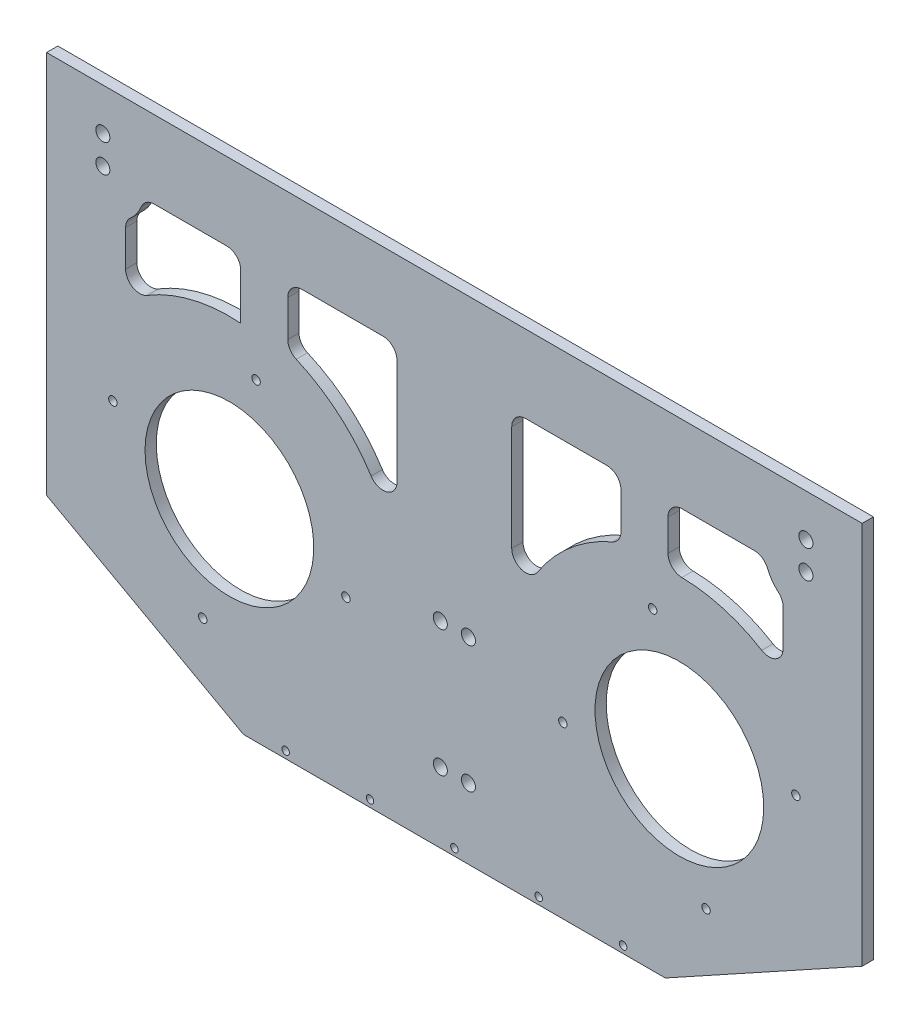
SolidWorks part; units mm, degrees
ref_plane "Front Plane" through (0, 0, 0) normal (0, 0, 1) x (1, 0, 0)
ref_plane "Top Plane" through (0, 0, 0) normal (0, 1, 0) x (1, 0, 0)
ref_plane "Right Plane" through (0, 0, 0) normal (1, 0, 0) x (0, 0, -1)
sketch "Sketch1" plane through (0, 0, 0) normal (0, 0, 1) x (1, 0, 0)
  line L0 (-125, 100) -> (125, 100) construction
  line L1 (-125, 0) -> (125, 0) construction
  line L2 (-145, -16.3871) -> (-75, -55)
  line L3 (-75, -55) -> (75, -55)
  line L4 (75, -55) -> (145, -16.3871)
  line L5 (-125, 105) -> (-125, 95) construction
  line L6 (0, -55) -> (0, 100) construction
  line L7 (-145, 120) -> (145, 120)
  line L8 (145, 120) -> (145, -16.3871)
  line L11 (-145, -16.3871) -> (-145, 120)
  line L12 (125, 105) -> (125, 95) construction
  line L13 (-5, -30) -> (5, -30) construction
  circle A0 centre (-125, 100) radius 12.5 construction
  circle A10 centre (-125, 0) radius 12.5 construction
  circle A11 centre (125, 0) radius 12.5 construction
  circle A12 centre (-125, 0) radius 17.5 construction
  circle A13 centre (-125, 100) radius 17.5 construction
  circle A25 centre (-125, 95) radius 2.5
  circle A26 centre (-125, 105) radius 2.5
  circle A27 centre (125, 95) radius 2.5
  circle A28 centre (125, 105) radius 2.5
  circle A29 centre (5, -30) radius 2.5
  circle A30 centre (-5, -30) radius 2.5
  point P12 (0, 100)
  point P15 (0, -30)
  point P45 (0, 120)
  dimension "D1" = 25
  dimension "D2" = 5
  dimension "D4" = 100
  dimension "D6" = 5
  dimension "D11" = 20
  dimension "D12" = 20
  dimension "D7" = 10
  dimension "D8" = 250
  dimension "D3" = 25
  dimension "D5" = 30
  dimension "D9" = 150
extrude "Boss-Extrude1" add sketch "Sketch1" along normal blind 4
sketch "Sketch2" plane through (0, 0, 4) normal (0, 0, 1) x (1, 0, 0)
  line L0 (121.4264, 24.4924) -> (38.5736, 5.5076) construction
  line L1 (89.4924, -26.4264) -> (70.5076, 56.4264) construction
  line L2 (0, 0) -> (0, 96.4486) construction
  line L3 (145, 120) -> (-145, 120) construction
  line L4 (-145, 120) -> (-145, -16.3871) construction
  line L5 (-80, 15) -> (80, 15) construction
  line L6 (-5, 15) -> (5, 15) construction
  circle A0 centre (80, 15) radius 42.5 construction
  circle A1 centre (38.5736, 5.5076) radius 1.5
  circle A2 centre (70.5076, 56.4264) radius 1.5
  circle A3 centre (121.4264, 24.4924) radius 1.5
  circle A4 centre (89.4924, -26.4264) radius 1.5
  circle A5 centre (80, 15) radius 30
  circle A6 centre (-38.5736, 5.5076) radius 1.5
  circle A7 centre (-70.5076, 56.4264) radius 1.5
  circle A8 centre (-89.4924, -26.4264) radius 1.5
  circle A9 centre (-121.4264, 24.4924) radius 1.5
  circle A10 centre (-80, 15) radius 42.5 construction
  circle A11 centre (-80, 15) radius 30
  circle A12 centre (-80, 15) radius 47.5 construction
  circle A15 centre (-5, 15) radius 2.5
  circle A16 centre (5, 15) radius 2.5
  point P6 (80, 15)
  point P27 (-80, 15)
  point P30 (0, 15)
  dimension "D1" = 85
  dimension "D2" = 3
  dimension "D3" = 60
  dimension "D4" = 95
  dimension "D5" = 5
  dimension "D6" = 105
  dimension "D7" = 65
  dimension "D8" = 10
extrude "Cut-Extrude1" cut sketch "Sketch2" against normal blind 10
sketch "Sketch3" plane through (0, 0, 4) normal (0, 0, 1) x (1, 0, 0)
  line L0 (-75, -55) -> (75, -55) construction
  circle A0 centre (0, -52.5) radius 1.325
  circle A1 centre (30, -52.5) radius 1.325
  circle A2 centre (60, -52.5) radius 1.325
  circle A3 centre (-30, -52.5) radius 1.325
  circle A4 centre (-60, -52.5) radius 1.325
  point P0 (0, -52.5)
  dimension "D2" = 2.65
  dimension "D1" = 2.5
  dimension "D4" = 30
  dimension "D6" = 30
extrude "Cut-Extrude2" cut sketch "Sketch3" against normal up to surface (4 mm away) up to face at (-122.9264, 24.4924, 0)
sketch "Sketch6" plane through (0, 0, 0) normal (0, 0, -1) x (-1, 0, 0)
  line L0 (-20.3921, 20.3957) -> (-20.3921, 92.4562)
  line L1 (-20.3921, 92.4562) -> (-59.2398, 92.4562)
  line L2 (-59.2398, 92.4562) -> (-59.2398, 71.1358)
  line L3 (-75.9623, 92.4562) -> (-110.4197, 92.4562)
  line L4 (-75.9623, 92.4562) -> (-75.9623, 71.1358)
  line L5 (-116.8961, 82.6152) -> (-116.8961, 57.4994)
  line L6 (0, -55) -> (0, 120) construction
  line L7 (75, -55) -> (-75, -55) construction
  line L8 (-145, 120) -> (145, 120) construction
  line L9 (20.3921, 20.3957) -> (20.3921, 92.4562)
  line L10 (20.3921, 92.4562) -> (59.2398, 92.4562)
  line L11 (59.2398, 92.4562) -> (59.2398, 71.1358)
  line L12 (75.9623, 92.4562) -> (75.9623, 71.1358)
  line L13 (75.9623, 92.4562) -> (110.4197, 92.4562)
  line L14 (116.8961, 82.6152) -> (116.8961, 57.4994)
  arc A0 (-20.3921, 20.3957) -> (-59.2398, 71.1358) centre (-80, 15) ccw
  arc A1 (-75.9623, 71.1358) -> (-116.8961, 57.4994) centre (-80, 15) ccw
  arc A2 (-110.4197, 92.4562) -> (-116.8961, 82.6152) centre (-125, 95) cw
  arc A3 (20.3921, 20.3957) -> (59.2398, 71.1358) centre (80, 15) cw
  arc A4 (75.9623, 71.1358) -> (116.8961, 57.4994) centre (80, 15) cw
  arc A5 (110.4197, 92.4562) -> (116.8961, 82.6152) centre (125, 95) ccw
extrude "Cut-Extrude3" cut sketch "Sketch6" along direction (0, 0, -1) on the side against the normal up to surface (4 mm away) contours L3 A2 L5 A1 L4 | A0 L0 L1 L2 | L9 A3 L11 L10 | A5 L13 L12 A4 L14 region at (36.1386, 72.1325, 0) region at (97.5349, 79.201, 0) region at (-36.1386, 72.1325, 0) region at (-97.5349, 79.201, 0) up to face at (-58.675, -52.5, 4)
fillet "Fillet1" radius 5 17 edges at (-59.2398, 92.4562, 2) (-110.4197, 92.4562, 2) (-116.8961, 82.6152, 2) (-59.2398, 71.1358, 2) (-116.8961, 57.4994, 2) (-75.9623, 92.4562, 2) (-20.3921, 92.4562, 2) (-20.3921, 20.3957, 2) (20.3921, 20.3957, 2) (59.2398, 92.4562, 2) (59.2398, 71.1358, 2) (20.3921, 92.4562, 2) (75.9623, 92.4562, 2) (75.9623, 71.1358, 2) (110.4197, 92.4562, 2) (116.8961, 82.6152, 2) (116.8961, 57.4994, 2)
equation "\"D1@Sketch1\" = \"cf_tube_outer_diameter\""
equation "\"mid_plate_mid_to_top\" = 100mm"
equation "\"mid_plate_mid_to_bottom\" = 30mm"
equation "\"mid_plate_horizontal_spacing\" = 250mm"
equation "\"cf_tube_outer_diameter\" = 25mm"
equation "\"D4@Sketch1\"=\"mid_plate_mid_to_top\""
equation "\"cf_tube_inner_diameter\" = 21mm"
equation "\"mid_tube_length\" = 500mm"
equation "\"cf_plate_thickness\" = 4mm"
equation "\"D1@Boss-Extrude1\"=\"cf_plate_thickness\""
equation "\"D8@Sketch1\"=\"mid_plate_horizontal_spacing\""
equation "\"D5@Sketch1\"=\"mid_plate_mid_to_bottom\""
equation "\"mid_plate_bottom_width\"= 150mm"
equation "\"D9@Sketch1\"=\"mid_plate_bottom_width\""
equation "\"mid_support_plate_distance\" = 250mm"
equation "\"nut_strip_2_hole_distance\" = 7mm"
equation "\"nut_strip_hole_diameter\" = 2.5mm"
equation "\"nut_strip_hole_to_edge_distance\" = 2.5mm"
equation "\"D1@Sketch3\"=\"nut_strip_hole_to_edge_distance\""
equation "\"D2@Sketch3\"=\"nut_strip_hole_diameter\"+0.15mm"
